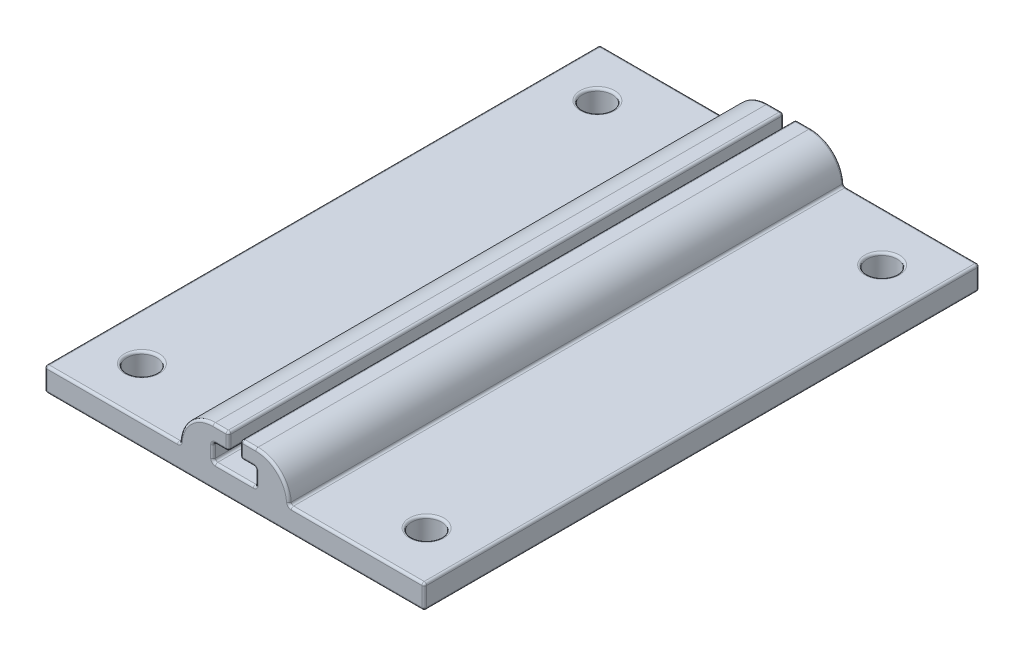
SolidWorks part; units mm, degrees
ref_plane "Front Plane" through (0, 0, 0) normal (0, 0, 1) x (1, 0, 0)
ref_plane "Top Plane" through (0, 0, 0) normal (0, 1, 0) x (1, 0, 0)
ref_plane "Right Plane" through (0, 0, 0) normal (1, 0, 0) x (0, 0, -1)
sketch "Sketch1" plane through (0, 0, 0) normal (0, 0, 1) x (1, 0, 0)
  line L0 (0, -28.2286) -> (0, 28.2286) construction
  line L1 (-40, -2.5) -> (40, -2.5)
  line L2 (-40, -2.5) -> (-40, 2.5)
  line L3 (-40, 2.5) -> (-11.5, 2.5)
  line L4 (40, -2.5) -> (40, 2.5)
  line L5 (-40, -2.5) -> (40, 2.5) construction
  line L6 (-40, 2.5) -> (40, -2.5) construction
  line L7 (-4.5, 2.5) -> (4.5, 2.5)
  line L8 (0, 2.5) -> (-4.5, 2.5) construction
  line L9 (0, 2.5) -> (0, 6) construction
  line L10 (0, 6) -> (-4.5, 6) construction
  line L12 (0, 6) -> (-1.25, 6) construction
  line L13 (0, 6) -> (0, 16.858) construction
  line L14 (0, 16.858) -> (-1.25, 16.858) construction
  line L15 (-1.25, 6) -> (-1.25, 16.858) construction
  line L16 (-4.5, 6) -> (-1.25, 6)
  line L17 (-4.5, 2.5) -> (-4.5, 6)
  line L18 (-4.5, 9.5) -> (-1.25, 9.5)
  line L19 (-1.25, 6) -> (-1.25, 9.5)
  line L20 (4.5, 2.5) -> (4.5, 6)
  line L21 (1.25, 6) -> (1.25, 9.5)
  line L22 (4.5, 6) -> (1.25, 6)
  line L23 (4.5, 9.5) -> (1.25, 9.5)
  line L24 (11.5, 2.5) -> (40, 2.5)
  arc A0 (-4.5, 9.5) -> (-11.5, 2.5) centre (-4.5, 2.5) ccw
  arc A1 (4.5, 9.5) -> (11.5, 2.5) centre (4.5, 2.5) cw
  point P0 (0, 0)
  point P9 (0, 0)
  dimension "D1" = 80
  dimension "D2" = 5
  dimension "D3" = 3.5
  dimension "D4" = 4.5
  dimension "D5" = 1.25
  dimension "D6" = 3.5
extrude "Boss-Extrude1" add sketch "Sketch1" along normal blind 58.5 and the other way blind 58.5 contours L7 L20 L22 L21 L23 A1 L24 L4 L1 L2 L3 A0 L18 L19 L16 L17
sketch "Sketch2" plane through (0, -2.5, 0) normal (0, -1, 0) x (1, 0, 0)
  line L0 (0, -58.5) -> (0, -52) construction
  line L2 (-40, -58.5) -> (40, -58.5) construction
  line L3 (0, 58.5) -> (0, 48) construction
  line L4 (-40, 58.5) -> (40, 58.5) construction
  line L5 (0, 48) -> (-30, 48) construction
  circle A0 centre (-30, 48) radius 3.15
  circle A1 centre (30, 48) radius 3.15
  circle A2 centre (30, -48) radius 3.15
  circle A3 centre (-30, -48) radius 3.15
  point P6 (0, 0)
  dimension "D4" = 6.3
  dimension "D1" = 10.5
  dimension "D2" = 6.5
  dimension "D3" = 30
  dimension "D5" = 2
  dimension "D6" = 2
extrude "Cut-Extrude1" cut sketch "Sketch2" against normal blind 58.5
fillet "Fillet1" radius 0.5 50 edges at (40, -2.5, 0) (-40, -2.5, 0) (-4.5, 6, 0) (-1.25, 6, 0) (-1.25, 9.5, 0) (1.25, 9.5, 0) (1.25, 6, 0) (4.5, 6, 0) (4.5, 2.5, 0) (-4.5, 2.5, 0) (-2.875, 6, -58.5) (-1.25, 7.75, -58.5) (-2.875, 9.5, -58.5) (-9.4497, 7.4497, -58.5) (-40, 0, -58.5) (0, -2.5, -58.5) (40, 0, -58.5) (9.4497, 7.4497, -58.5) (2.875, 9.5, -58.5) (1.25, 7.75, -58.5) (2.875, 6, -58.5) (4.5, 4.25, -58.5) (0, 2.5, -58.5) (-4.5, 4.25, -58.5) (0, 2.5, 58.5) (4.5, 4.25, 58.5) (2.875, 6, 58.5) (1.25, 7.75, 58.5) (2.875, 9.5, 58.5) (9.4497, 7.4497, 58.5) (40, 0, 58.5) (0, -2.5, 58.5) (-40, 0, 58.5) (-9.4497, 7.4497, 58.5) (-2.875, 9.5, 58.5) (-1.25, 7.75, 58.5) (-2.875, 6, 58.5) (-4.5, 4.25, 58.5) (-25.75, 2.5, -58.5) (-11.5, 2.5, 0) (-25.75, 2.5, 58.5) (-40, 2.5, 0) (-30, 2.5, -51.15) (-30, 2.5, 44.85) (25.75, 2.5, -58.5) (40, 2.5, 0) (25.75, 2.5, 58.5) (11.5, 2.5, 0) (33.15, 2.5, 48) (33.15, 2.5, -48)
